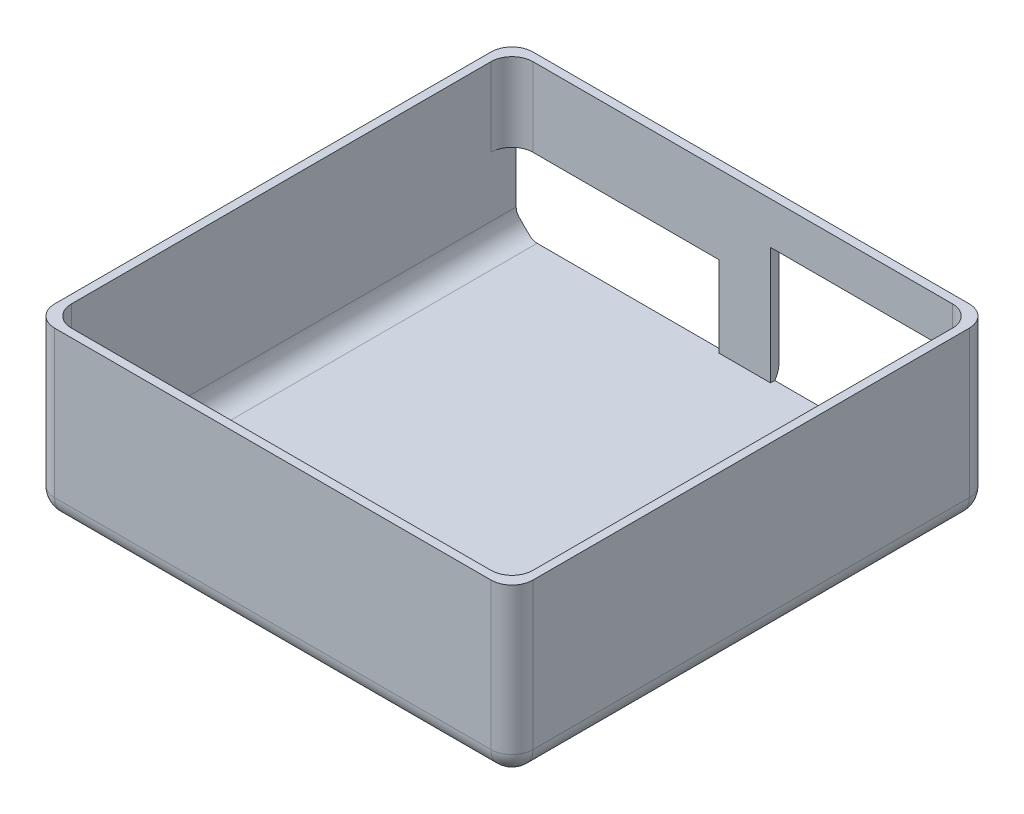
SolidWorks part; units mm, degrees
ref_plane "Front Plane" through (0, 0, 0) normal (0, 0, 1) x (1, 0, 0)
ref_plane "Top Plane" through (0, 0, 0) normal (0, 1, 0) x (1, 0, 0)
ref_plane "Right Plane" through (0, 0, 0) normal (1, 0, 0) x (0, 0, -1)
sketch "Sketch1" plane through (0, 0, 0) normal (0, 1, 0) x (1, 0, 0)
  line L0 (0, 15.3651) -> (0, -12.9206) construction
  line L1 (-55, 55) -> (55, 55)
  line L2 (-55, 55) -> (-55, -55)
  line L3 (-55, -55) -> (55, -55)
  line L4 (55, 55) -> (55, -55)
  line L5 (-14.8413, 0) -> (25.6667, 0) construction
  line L6 (-57, 57) -> (-57, -57)
  line L7 (-57, -57) -> (57, -57)
  line L8 (57, 57) -> (57, -57)
  line L9 (-57, 57) -> (57, 57)
  dimension "D1" = 110
  dimension "D2" = 110
  dimension "D3" = 2
extrude "Boss-Extrude1" add sketch "Sketch1" along normal blind 2 contours L4 L1 L2 L3 | L9 L6 L7 L8 L1 L4 L3 L2 region at (0, 0, 0) region at (0, 0, -55.3878)
extrude "Boss-Extrude2" add sketch "Sketch1<3>" along normal blind 40 contours L9 L6 L7 L8 L1 L4 L3 L2 region at (0, 0, -55.3878)
sketch "Sketch1<3>" plane through (0, 0, 0) normal (0, 1, 0) x (1, 0, 0) same geometry as "Sketch1"
sketch "Sketch2" plane through (0, 0, -55) normal (0, 0, 1) x (1, 0, 0)
  line L0 (55, 40) -> (55, 2) construction
  line L1 (55, 2) -> (0, 2)
  line L2 (55, 2) -> (55, 29.9645)
  line L3 (55, 29.9645) -> (0, 29.9645)
  line L4 (0, 2) -> (0, 29.9645)
  line L5 (55, 2) -> (-55, 2) construction
  line L6 (0, 21.287) -> (-55, 21.287)
  line L7 (0, 21.287) -> (0, 2)
  line L8 (0, 2) -> (-55, 2)
  line L9 (-55, 21.287) -> (-55, 2)
  line L10 (-5.6499, 21.287) -> (-5.6499, 2)
  line L11 (6.6223, 29.9645) -> (6.6223, 2)
  line M9 (-55, 2) -> (55, 2)
  line M10 (55, 2) -> (55, 40)
  line M12 (-55, 40) -> (-55, 2)
extrude "Cut-Extrude1" cut sketch "Sketch2" against normal through all contours L3 L11 L1 M10 | L10 L6 M12 M9 region at (30.8112, 15.9823, -55) region at (-30.325, 11.6435, -55)
fillet "Fillet1" radius 5 12 edges at (-55, 2, -1) (0, 2, 55) (55, 2, -1) (0, 0, 57) (-57, 20, 57) (-55, 21, 55) (55, 21, 55) (57, 20, 57) (57, 20, -57) (55, 34.9823, -55) (-55, 30.6435, -55) (-57, 20, -57)
fillet "Fillet2" radius 5 7 edges at (55.5355, 1.4645, 55.5355) (57, 0, 0) (55.5355, 0, -55.5355) (0, 0, -57) (-55.5355, 0, -55.5355) (-55.5355, 1.4645, 55.5355) (-57, 0, 0)
